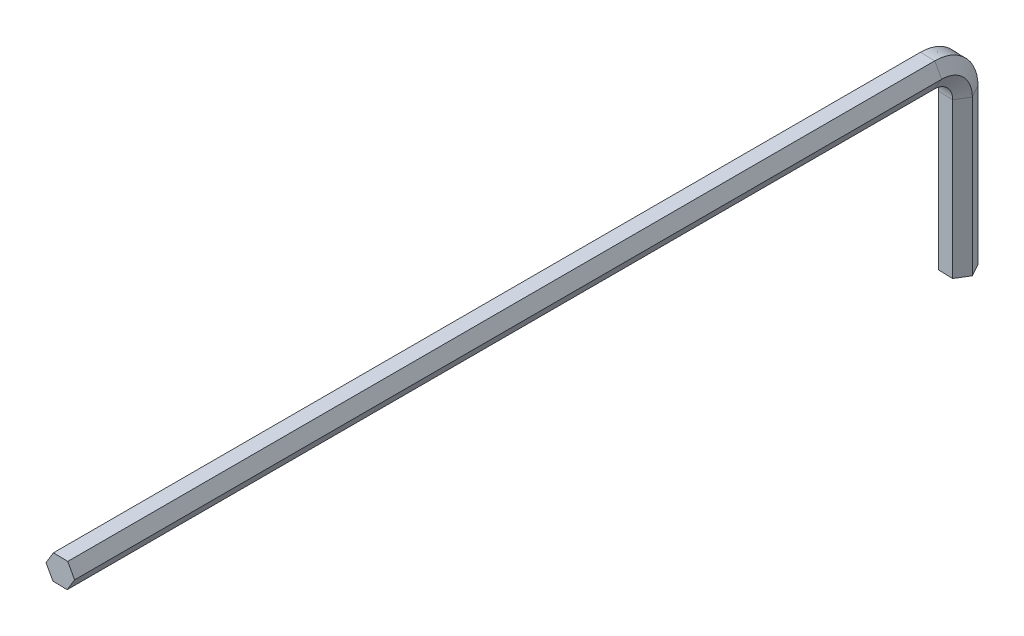
SolidWorks part; units mm, degrees
material "1060 Alloy"
ref_plane "Front Plane" through (0, 0, 0) normal (1, 0, 0) x (0, 1, 0)
ref_plane "Top Plane" through (0, 0, 0) normal (0, 0, 1) x (0, 1, 0)
ref_plane "Right Plane" through (0, 0, 0) normal (0, 1, 0) x (-1, 0, 0)
sketch3d "3DSketch1"
  line L0 (0, 0, 0) -> (0, 25, 0)
  line L1 (0, 30, 5) -> (0, 30, 145)
  arc A0 (0, 30, 5) -> (0, 25, 0) centre (0, 25, 5) ccw
  point P6 (0, 30, 0)
  point P7 (-5, 25, 5)
  dimension "D1" = 5
  dimension "D2" = 30
  dimension "D3" = 145
sketch "Sketch1" plane through (0, 0, 0) normal (0, 1, 0) x (-1, 0, 0)
  line L0 (2.3089, -0.0493) -> (1.1971, 1.9749)
  line L1 (-1.1117, 2.0242) -> (-2.3089, 0.0493)
  line L2 (-2.3089, 0.0493) -> (-1.1971, -1.9749)
  line L3 (-1.1971, -1.9749) -> (1.1117, -2.0242)
  line L4 (1.1117, -2.0242) -> (2.3089, -0.0493)
  line L5 (1.1971, 1.9749) -> (-1.1117, 2.0242)
  circle A1 centre (0, 0) radius 2 construction
  dimension "D1" = 4
sweep "Sweep1" add profiles "Sketch1" path "3DSketch1"
